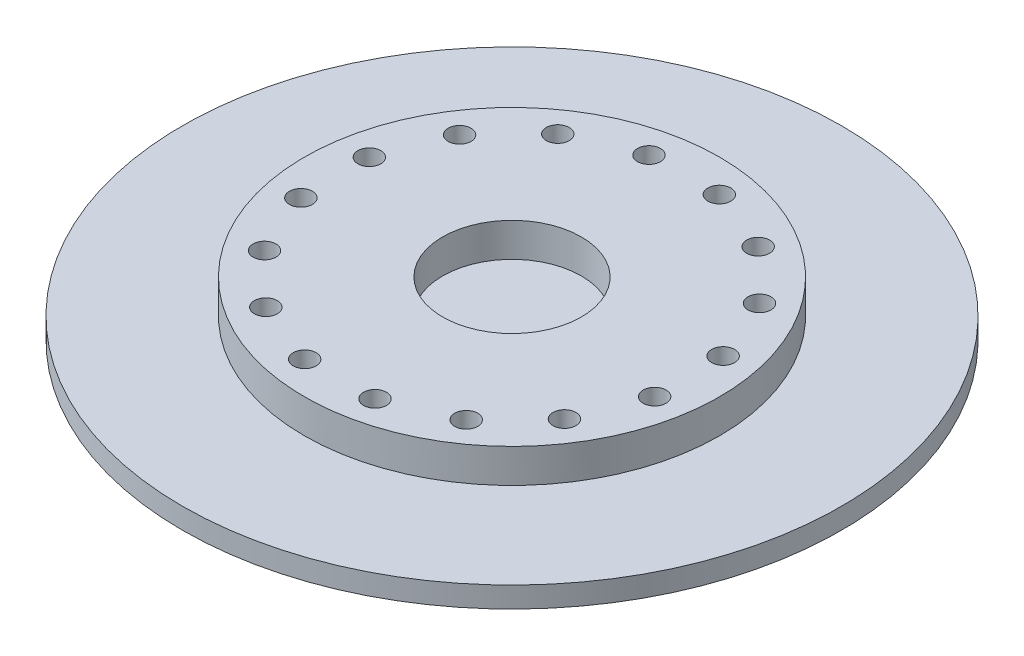
SolidWorks part; units mm, degrees
ref_plane "Front Plane" through (0, 0, 0) normal (0, 0, 1) x (1, 0, 0)
ref_plane "Top Plane" through (0, 0, 0) normal (0, 1, 0) x (1, 0, 0)
ref_plane "Right Plane" through (0, 0, 0) normal (1, 0, 0) x (0, 0, -1)
sketch "Sketch1" plane through (0, 0, 0) normal (0, 1, 0) x (1, 0, 0)
  line L1 (0, 0) -> (-84.2396, -211.4133) construction
  circle A0 centre (0, 0) radius 120.65
  dimension "D1" = 241.3
extrude "Extrude1" add sketch "Sketch1" along normal blind 7.62
sketch "Sketch2" plane through (0, 0, 0) normal (0, -1, 0) x (1, 0, 0)
  circle A0 centre (0, 0) radius 76
  circle A1 centre (0, 0) radius 25.4
  dimension "OD" = 152
  dimension "ID" = 50.8
extrude "Extrude2" add sketch "Sketch2" against normal blind 20
ref_axis "Sniffer Axis" through (0, 0, 0) along (-0.3702, 0, 0.929)
sketch "Sketch5" plane through (0, 0, 0) normal (0, -1, 0) x (1, 0, 0)
  line L0 (0, 0) -> (-77.775, 195.1894) construction
  line L1 (28.8693, -70.3079) -> (27.3945, -70.8955)
  line L2 (74031.306, -185793.8797) -> (-74115.5456, 186005.293) construction
  line L3 (0, 0) -> (-208.5489, -83.0982) construction
  line L4 (-27.3945, 70.8955) -> (-28.8693, 70.3079)
  line L5 (-28.8693, 70.3079) -> (27.3945, -70.8955)
  line L7 (-27.3945, 70.8955) -> (28.8693, -70.3079)
  point P4 (28.1319, -70.6017)
  point P8 (18.804, -47.1916)
  point P13 (-18.804, 47.1916)
  point P14 (-28.1319, 70.6017)
  point P15 (0.7374, 0.2938)
  point P16 (-0.7374, -0.2938)
  dimension "D2" = 1.5875
extrude "Extrude3" cut sketch "Sketch5" against normal blind 1.016
sketch "Sketch8" plane through (0, 0, 0) normal (0, -1, 0) x (1, 0, 0)
  line L0 (0, 0) -> (-11.845, 64.0642) construction
  line L1 (74031.306, -185793.8797) -> (-74115.5456, 186005.293) construction
  circle A0 centre (-11.845, 64.0642) radius 4.2
  dimension "D3" = 8.4
  dimension "D1" = 11.25
  dimension "D2" = 65.15
extrude "Extrude4" cut sketch "Sketch8" against normal up to next
pattern_circular "CirPattern1" count 16 over 360 about axis through (0, 20, 0) along (0, -1, 0) of "Extrude4"
equation "\"OD\"=5.984252"
equation "\"L\"=231.8"
equation "\"d\"=24.5"
equation "\"A\"=24"
equation "\"H\"=8.4"
equation "\"S\"=217"
equation "\"ID\"=2.000000"
